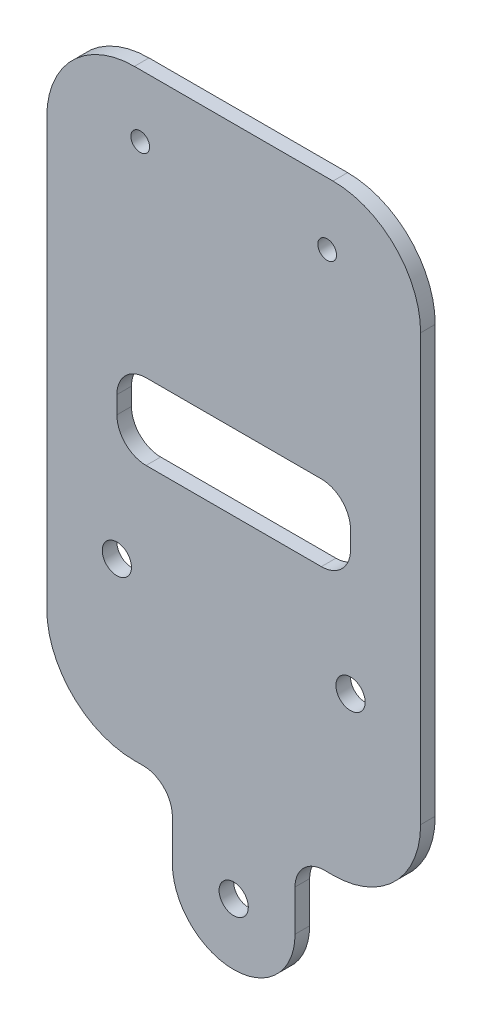
SolidWorks part; units mm, degrees
material "2024 Alloy"
ref_plane "Front Plane" through (0, 0, 0) normal (0, 0, 1) x (1, 0, 0)
ref_plane "Top Plane" through (0, 0, 0) normal (0, 1, 0) x (1, 0, 0)
ref_plane "Right Plane" through (0, 0, 0) normal (1, 0, 0) x (0, 0, -1)
sketch "Sketch2" plane through (0, 0, 0) normal (0, 0, 1) x (1, 0, 0)
  line L1 (-100, 100) -> (100, 100)
  line L2 (-100, 100) -> (-100, -100)
  line L3 (-100, -100) -> (100, -100)
  line L4 (100, 100) -> (100, -100)
  line L5 (-100, 100) -> (100, -100) construction
  line L6 (-100, -100) -> (100, 100) construction
  point P0 (0, 0)
  dimension "D1" = 200
extrude "Boss-Extrude1" add sketch "Sketch2" along normal blind 2.5
sketch "Sketch3" plane through (0, 0, 0) normal (0, 0, -1) x (-1, 0, 0)
  line L1 (-44.5, 23.75) -> (44.5, 23.75) construction
  line L2 (-44.5, 23.75) -> (-44.5, -23.75) construction
  line L3 (-44.5, -23.75) -> (44.5, -23.75) construction
  line L4 (44.5, 23.75) -> (44.5, -23.75) construction
  line L5 (-44.5, 23.75) -> (44.5, -23.75) construction
  line L6 (-44.5, -23.75) -> (44.5, 23.75) construction
  circle A0 centre (-32.4, 11.65) radius 2.5
  circle A1 centre (7.6, 11.65) radius 2.5
  circle A2 centre (-12.4, -28.75) radius 2.5
  point P0 (0, 0)
  dimension "D7" = 5
  dimension "D1" = 89
  dimension "D2" = 47.5
  dimension "D3" = 12.1
  dimension "D4" = 12.1
  dimension "D5" = 12.1
  dimension "D6" = 40
  dimension "D8" = 20
  dimension "D9" = 5
extrude "Cut-Extrude1" cut sketch "Sketch3" against normal blind 10
sketch "Sketch4" plane through (0, 0, 2.5) normal (0, 0, 1) x (1, 0, 0)
  line L1 (-19.6, 86.1635) -> (44.4, 86.1635)
  line L5 (32.4, 11.65) -> (32.4, 28) construction
  line L6 (-7.6, 11.65) -> (-7.6, 28) construction
  line L7 (-19.6, 28.331) -> (-19.6, 86.1635)
  line L8 (44.4, 28.331) -> (44.4, -16.75)
  line L10 (22.9, -28.75) -> (22.9, -16.75)
  line L11 (1.9, -34.4037) -> (1.9, -16.75)
  line L12 (1.9, -16.75) -> (-19.6, -16.75)
  line L13 (-19.6, -16.75) -> (-19.6, 28.331)
  line L14 (22.9, -16.75) -> (44.4, -16.75)
  line L15 (44.4, 28.331) -> (44.4, 86.1635)
  line L16 (25.9, 60.853) -> (25.9, 34.5762) construction
  line L17 (25.9, 55.5) -> (25.9, 73.5) construction
  line L18 (-1.9, 60.853) -> (-1.9, 34.5762) construction
  line L19 (-1.9, 55.5) -> (-1.9, 73.5) construction
  line L20 (12, 59.8279) -> (12, 40.2509) construction
  line L22 (0.825, 49.5) -> (23.175, 49.5) construction
  line L23 (0.825, 49.5) -> (0.825, 26.5) construction
  line L24 (0.825, 26.5) -> (23.175, 26.5) construction
  line L25 (23.175, 49.5) -> (23.175, 26.5) construction
  line L26 (0.825, 49.5) -> (23.175, 26.5) construction
  line L27 (0.825, 26.5) -> (23.175, 49.5) construction
  line L28 (30.15, 49.5) -> (-6.15, 49.5) construction
  line L30 (-7.6, 41) -> (32.4, 41)
  line L31 (-7.6, 41) -> (-7.6, 28)
  line L32 (-7.6, 28) -> (32.4, 28)
  line L33 (32.4, 41) -> (32.4, 28)
  line L34 (-7.6, 41) -> (32.4, 28) construction
  line L35 (-7.6, 28) -> (32.4, 41) construction
  circle A2 centre (12.4, -28.75) radius 10.5
  point P0 (12.4, 34.5)
  point P20 (12.4, 86.1635)
  point P36 (12, 38)
  line M6 (100, -100) -> (100, 100)
  line M7 (100, 100) -> (-100, 100)
  line M8 (-100, 100) -> (-100, -100)
  line M9 (-100, -100) -> (100, -100)
  dimension "D5" = 21
  dimension "D1" = 8.5
  dimension "D2" = 13
  dimension "D3" = 64
  dimension "D6" = 23
  dimension "D7" = 22.35
  dimension "D8" = 40
extrude "Cut-Extrude2" cut sketch "Sketch4" against normal up to next contours A2 L11 L12 L13 L7 L15 L8 L14 L10 M7 M8 M9 M6 | L33 L30 L31 L32 region at (12.4, 34.5, 2.5) region at (0, -97.1716, 2.5)
fillet "Fillet1" radius 15 4 edges at (-19.6, -16.75, 1.25) (44.4, -16.75, 1.25) (-19.6, 86.1635, 1.25) (44.4, 86.1635, 1.25)
fillet "Fillet2" radius 5 6 edges at (-7.6, 41, 1.25) (-7.6, 28, 1.25) (32.4, 41, 1.25) (32.4, 28, 1.25) (1.9, -16.75, 1.25) (22.9, -16.75, 1.25)
sketch "Sketch6" plane through (0, 0, 2.5) normal (0, 0, 1) x (1, 0, 0)
  line L0 (-19.6, 71.1635) -> (-19.6, -1.75) construction
  line L1 (12.4, 15.6544) -> (12.4, 118.239) construction
  line L12 (27.4, 41) -> (-2.6, 41) construction
  circle A0 centre (-3.6, 75.5) radius 1.6
  circle A1 centre (28.4, 75.5) radius 1.6
  dimension "D1" = 3.2
  dimension "D3" = 34.5
  dimension "D2" = 16
extrude "Cut-Extrude4" cut sketch "Sketch6" against normal up to next contours A1 | A0 region at (-3.6, 75.5, 2.5) region at (28.4, 75.5, 2.5)
